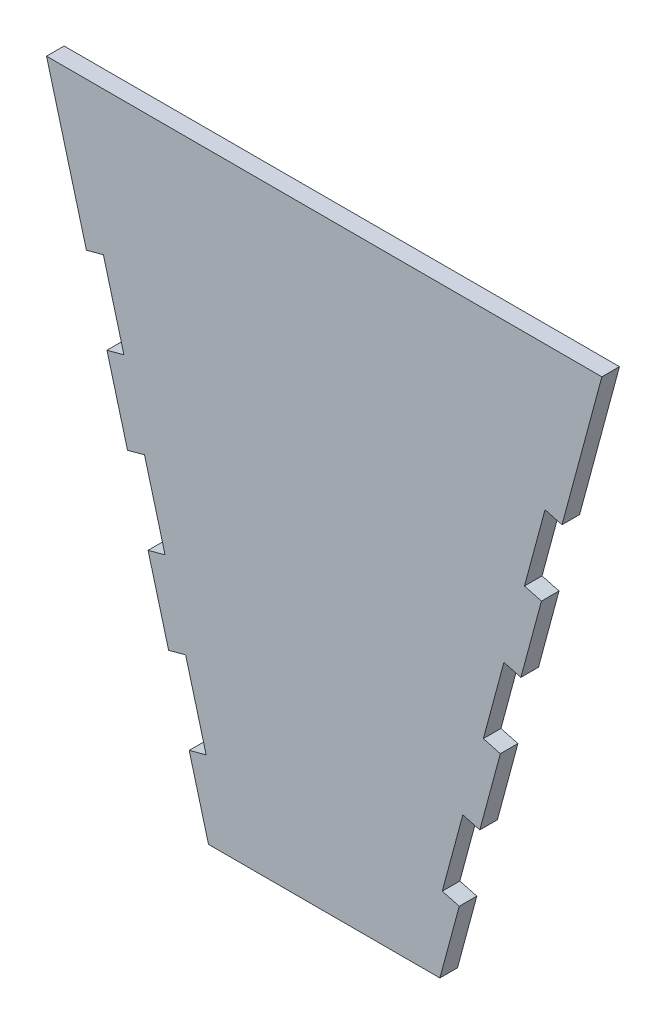
SolidWorks part; units mm, degrees
ref_plane "Front Plane" through (0, 0, 0) normal (0, 0, 1) x (1, 0, 0)
ref_plane "Top Plane" through (0, 0, 0) normal (0, 1, 0) x (1, 0, 0)
ref_plane "Right Plane" through (0, 0, 0) normal (1, 0, 0) x (0, 0, -1)
sketch "Sketch1" plane through (0, 0, 0) normal (0, 0, 1) x (1, 0, 0)
  line L0 (0, 165.1) -> (44.45, 0)
  line L1 (0, 0) -> (152.4, 0)
  line L2 (0, 0) -> (0, 165.1)
  line L3 (0, 165.1) -> (152.4, 165.1)
  line L4 (152.4, 0) -> (152.4, 165.1)
  line L6 (152.4, 165.1) -> (107.95, 0)
  dimension "D1" = 152.4
  dimension "D2" = 165.1
  dimension "D3" = 44.45
  dimension "D4" = 44.45
extrude "Boss-Extrude1" add sketch "Sketch1" along normal blind 4.826 contours L6 L3 L0 L1 region at (76.2, 93.8804, 0)
sketch "Sketch2" plane through (0, 0, 4.826) normal (0, 0, 1) x (1, 0, 0)
  line L0 (76.2, 0) -> (76.2, 165.1) construction
  line L1 (10.9436, 124.4523) -> (15.6037, 125.7069)
  line L2 (0, 165.1) -> (44.45, 0) construction
  line L3 (15.6037, 125.7069) -> (21.2444, 104.7558)
  line L4 (21.2444, 104.7558) -> (16.5843, 103.5012)
  line L5 (16.5843, 103.5012) -> (10.9436, 124.4523)
  line L6 (22.225, 82.55) -> (26.8851, 83.8046)
  line L7 (26.8851, 83.8046) -> (32.5258, 62.8535)
  line L8 (32.5258, 62.8535) -> (27.8657, 61.5988)
  line L9 (27.8657, 61.5988) -> (22.225, 82.55)
  line L10 (33.5064, 40.6477) -> (38.1665, 41.9023)
  line L11 (38.1665, 41.9023) -> (43.8072, 20.9512)
  line L12 (43.8072, 20.9512) -> (39.1471, 19.6965)
  line L13 (39.1471, 19.6965) -> (33.5064, 40.6477)
  line L14 (0, 165.1) -> (152.4, 165.1) construction
  line L16 (21.2444, 104.7558) -> (26.8851, 83.8046) construction
  line L17 (32.5258, 62.8535) -> (38.1665, 41.9023) construction
  line L18 (43.8072, 20.9512) -> (49.4478, 0) construction
  line L19 (44.45, 0) -> (107.95, 0) construction
  line L20 (108.5928, 20.9512) -> (102.9522, 0) construction
  line L21 (119.8742, 62.8535) -> (114.2335, 41.9023) construction
  line L22 (131.1556, 104.7558) -> (125.5149, 83.8046) construction
  line L23 (113.2529, 19.6965) -> (118.8936, 40.6477)
  line L24 (108.5928, 20.9512) -> (113.2529, 19.6965)
  line L25 (114.2335, 41.9023) -> (108.5928, 20.9512)
  line L26 (118.8936, 40.6477) -> (114.2335, 41.9023)
  line L27 (124.5343, 61.5988) -> (130.175, 82.55)
  line L28 (119.8742, 62.8535) -> (124.5343, 61.5988)
  line L29 (125.5149, 83.8046) -> (119.8742, 62.8535)
  line L30 (130.175, 82.55) -> (125.5149, 83.8046)
  line L31 (135.8157, 103.5012) -> (141.4564, 124.4523)
  line L32 (131.1556, 104.7558) -> (135.8157, 103.5012)
  line L33 (136.7963, 125.7069) -> (131.1556, 104.7558)
  line L34 (141.4564, 124.4523) -> (136.7963, 125.7069)
  line L35 (43.8072, 20.9512) -> (49.4478, 0) construction
  dimension "D1" = 4.826
extrude "Cut-Extrude1" cut sketch "Sketch2" against normal through all
equation "\"MDF\"= 0.19in"
equation "\"PVCID\" = 2.067in"
equation "\"PVCOD\" = 2.375in"
equation "\"GenDiameter\"= 60mm"
equation "\"GenCutDiameter\" = 1.8in"
equation "\"GenCutDistance\" = 1"
equation "\"TowerHeight\" = 6in"
equation "\"TowerFrontBase\" = 3in"
equation "\"FunnelHeight\" = 1in"
equation "\"FunnelAngle\" = 20"
equation "\"TowerSideBase\" = 3in"
equation "\"TowerPanelLength\" = 2in"
equation "\"TowerPanelLeeway\" = 0.5in"
equation "\"BaseLength\" = 9in"
equation "\"BaseWidth\" = 10in"
equation "\"WheelHoleLength\" = 3.25in"
equation "\"WheelHoleWidth\" = 26mm"
equation "\"WheelHoleFromBack\" = 1.5in"
equation "\"DropLength\" = 1in"
equation "\"DropWidth\" = 8.5in"
equation "\"BumperWidth\" = 2in"
equation "\"SmallHexDiameter\" = 0.185in"
equation "\"SmallHexHeight\" = 0.701in"
equation "\"ScrewSize\" = 0.106in"
equation "\"BigHexDiameter\" = 0.251in"
equation "\"BigHexHeight\" = 0.374in"
equation "\"PCBThickness\" = 0.066in"
equation "\"ConnectorHeight\" = 0.517in"
equation "\"BoardHeight\" = 0.583in"
equation "\"UnoStackHeight\" = 1.351in"
equation "\"UnoStackWidth\" = 3.053in"
equation "\"UnoStackLength\" = 3.152in"
equation "\"HBridgeWidth\" = 1.797in"
equation "\"HBridgeLength\" = 2.236in"
equation "\"DSWidth\" = 1.820in"
equation "\"DSLength\" = 1.833in"
equation "\"StepperWidth\" = 1.799in"
equation "\"StepperLength\" = 2.248in"
equation "\"ULNWidth\" = 1.304in"
equation "\"ULNLength\" = 1.545in"
equation "\"VSwitchHeight\" = 0.392in"
equation "\"VSwitchWidth\" = 0.637in"
equation "\"VSwitchLength\" = 1.097in"
equation "\"SkateWheelDiameter\" = 80mm"
equation "\"SkateWheelThickness\" = 24mm"
equation "\"BaseDistance\" = 3in"
equation "\"DummyVar\" = 2in"
equation "\"D1@Boss-Extrude1\"=\"MDF\""
equation "\"D1@Sketch2\"=\"MDF\""
